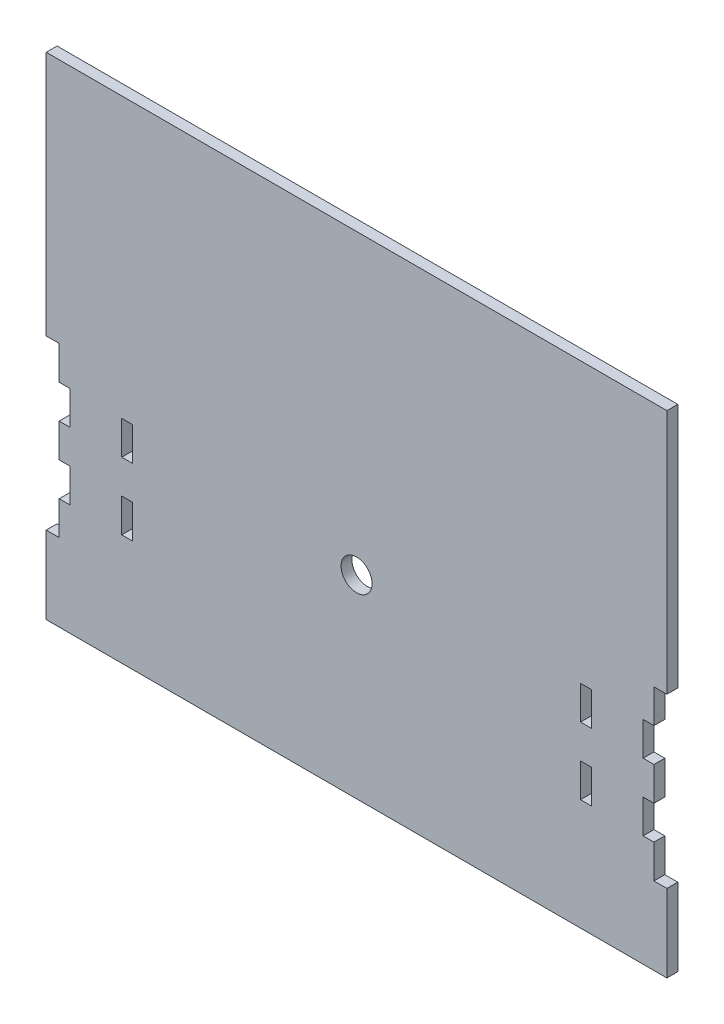
SolidWorks part; units mm, degrees
ref_plane "Front Plane" through (0, 0, 0) normal (0, 0, 1) x (1, 0, 0)
ref_plane "Top Plane" through (0, 0, 0) normal (0, 1, 0) x (1, 0, 0)
ref_plane "Right Plane" through (0, 0, 0) normal (1, 0, 0) x (0, 0, -1)
sketch "Sketch1" plane through (0, 0, 0) normal (0, 0, 1) x (1, 0, 0)
  line L1 (-152.4, 120.65) -> (152.4, 120.65)
  line L2 (-152.4, 120.65) -> (-152.4, -120.65)
  line L3 (-152.4, -120.65) -> (152.4, -120.65)
  line L4 (152.4, 120.65) -> (152.4, -120.65)
  line L5 (-152.4, 120.65) -> (152.4, -120.65) construction
  line L6 (-152.4, -120.65) -> (152.4, 120.65) construction
  point P0 (0, 0)
  dimension "D1" = 241.3
  dimension "D2" = 304.8
extrude "Boss-Extrude1" add sketch "Sketch1" along normal blind 5.334
sketch "Sketch2" plane through (0, 0, 0) normal (0, 0, -1) x (-1, 0, 0)
  line L0 (152.4, 120.65) -> (152.4, -120.65) construction
  line L1 (152.4, 0) -> (146.05, 0)
  line L2 (152.4, 0) -> (152.4, -82.55)
  line L3 (152.4, -82.55) -> (146.05, -82.55)
  line L4 (146.05, 0) -> (146.05, -82.55)
  line L5 (-152.4, -120.65) -> (-152.4, 120.65) construction
  line L6 (-152.4, 0) -> (-146.05, 0)
  line L7 (-152.4, 0) -> (-152.4, -82.55)
  line L8 (-152.4, -82.55) -> (-146.05, -82.55)
  line L9 (-146.05, 0) -> (-146.05, -82.55)
  line L10 (152.4, -120.65) -> (-152.4, -120.65) construction
  dimension "D1" = 82.55
  dimension "D2" = 82.55
  dimension "D3" = 38.1
  dimension "D4" = 38.1
  dimension "D5" = 6.35
  dimension "D6" = 6.35
extrude "Cut-Extrude1" cut sketch "Sketch2" against normal through all
sketch "Sketch9" plane through (0, 0, 5.334) normal (0, 0, 1) x (1, 0, 0)
  line L0 (-146.05, 0) -> (-146.05, -82.55) construction
  line L1 (-146.05, -16.51) -> (-140.716, -16.51)
  line L2 (-146.05, -16.51) -> (-146.05, -33.02)
  line L3 (-146.05, -33.02) -> (-140.716, -33.02)
  line L4 (-140.716, -16.51) -> (-140.716, -33.02)
  line L5 (-146.05, 0) -> (-140.716, 0) construction
  line L6 (-146.05, -49.53) -> (-140.716, -49.53)
  line L7 (-146.05, -49.53) -> (-146.05, -66.04)
  line L8 (-146.05, -66.04) -> (-140.716, -66.04)
  line L9 (-140.716, -49.53) -> (-140.716, -66.04)
  line L10 (-140.716, 0) -> (-140.716, -16.51) construction
  line L11 (-140.716, -33.02) -> (-140.716, -49.53) construction
  line L12 (-146.05, -82.55) -> (-140.716, -82.55) construction
  line L13 (-140.716, -82.55) -> (-140.716, -66.04) construction
  line L14 (0, -120.65) -> (0, 120.65) construction
  line L15 (-152.4, -120.65) -> (152.4, -120.65) construction
  line L16 (152.4, 120.65) -> (-152.4, 120.65) construction
  line L17 (140.716, -82.55) -> (140.716, -66.04) construction
  line L18 (146.05, -82.55) -> (140.716, -82.55) construction
  line L19 (140.716, -33.02) -> (140.716, -49.53) construction
  line L20 (140.716, 0) -> (140.716, -16.51) construction
  line L21 (146.05, 0) -> (140.716, 0) construction
  line L22 (140.716, -49.53) -> (140.716, -66.04)
  line L23 (146.05, -66.04) -> (140.716, -66.04)
  line L24 (146.05, -49.53) -> (146.05, -66.04)
  line L25 (146.05, -49.53) -> (140.716, -49.53)
  line L26 (140.716, -16.51) -> (140.716, -33.02)
  line L27 (146.05, -33.02) -> (140.716, -33.02)
  line L28 (146.05, -16.51) -> (146.05, -33.02)
  line L29 (146.05, -16.51) -> (140.716, -16.51)
  dimension "D1" = 5.334
extrude "Cut-Extrude2" cut sketch "Sketch9" against normal through all
sketch "Sketch23" plane through (0, 0, 5.334) normal (0, 0, 1) x (1, 0, 0)
  line L0 (-140.716, -24.765) -> (-61.976, -24.765) construction
  line L1 (-140.716, -33.02) -> (-140.716, -16.51) construction
  line L2 (-140.716, -16.51) -> (-109.982, -16.51) construction
  line L3 (-140.716, -33.02) -> (-109.982, -33.02) construction
  line L4 (-146.05, -41.275) -> (146.05, -41.275) construction
  line L5 (-146.05, -33.02) -> (-146.05, -49.53) construction
  line L6 (146.05, -49.53) -> (146.05, -33.02) construction
  line L7 (-140.716, -49.53) -> (-109.982, -49.53) construction
  line L8 (-140.716, -57.785) -> (-61.976, -57.785) construction
  line L9 (-140.716, -66.04) -> (-109.982, -66.04) construction
  line L10 (0, -120.65) -> (0, 120.65) construction
  line L11 (-152.4, -120.65) -> (152.4, -120.65) construction
  line L12 (152.4, 120.65) -> (-152.4, 120.65) construction
  line L13 (140.716, -66.04) -> (109.982, -66.04) construction
  line L14 (140.716, -49.53) -> (109.982, -49.53) construction
  line L15 (140.716, -33.02) -> (109.982, -33.02) construction
  line L16 (140.716, -16.51) -> (109.982, -16.51) construction
  line L17 (-109.982, -66.04) -> (-115.316, -66.04)
  line L18 (109.982, -16.51) -> (115.316, -16.51)
  line L19 (109.982, -16.51) -> (109.982, -33.02)
  line L20 (109.982, -33.02) -> (115.316, -33.02)
  line L21 (115.316, -16.51) -> (115.316, -33.02)
  line L22 (109.982, -49.53) -> (115.316, -49.53)
  line L23 (109.982, -49.53) -> (109.982, -66.04)
  line L24 (109.982, -66.04) -> (115.316, -66.04)
  line L25 (115.316, -49.53) -> (115.316, -66.04)
  line L26 (-115.316, -49.53) -> (-115.316, -66.04)
  line L27 (-109.982, -49.53) -> (-109.982, -66.04)
  line L28 (-109.982, -49.53) -> (-115.316, -49.53)
  line L29 (-109.982, -33.02) -> (-115.316, -33.02)
  line L30 (-115.316, -16.51) -> (-115.316, -33.02)
  line L31 (-109.982, -16.51) -> (-115.316, -16.51)
  line L32 (-109.982, -16.51) -> (-109.982, -33.02)
  line L33 (140.716, -16.51) -> (140.716, -33.02) construction
  dimension "D1" = 5.334
  dimension "D2" = 5.334
  dimension "D3" = 25.4
  dimension "D4" = 25.4
extrude "Cut-Extrude8" cut sketch "Sketch23" against normal through all
sketch "Sketch24" plane through (0, 0, 0) normal (0, 0, -1) x (-1, 0, 0)
  line L0 (152.4, -101.6) -> (-152.4, -101.6) construction
  line L1 (152.4, -82.55) -> (152.4, -120.65) construction
  line L2 (-152.4, -120.65) -> (-152.4, -82.55) construction
  line L3 (0, -120.65) -> (0, 120.65) construction
  line L4 (152.4, -120.65) -> (-152.4, -120.65) construction
  line L5 (-152.4, 120.65) -> (152.4, 120.65) construction
  circle A0 centre (0, -25.4) radius 7.62
  dimension "D2" = 15.24
  dimension "D1" = 76.2
  dimension "D3" = 0
extrude "Cut-Extrude9" cut sketch "Sketch24" against normal through all
equation "\"MDF\" = .21"
equation "\"Foamcore\"= .13in"
equation "\"Gmaterial\"= \"MDF\""
equation "\"D1@Sketch9\"=\"MDF\""
equation "\"D1@Sketch23\"=\"MDF\""
equation "\"D2@Sketch23\"=\"D1@Sketch23\""
equation "\"D1@Boss-Extrude1\"=\"MDF\""
